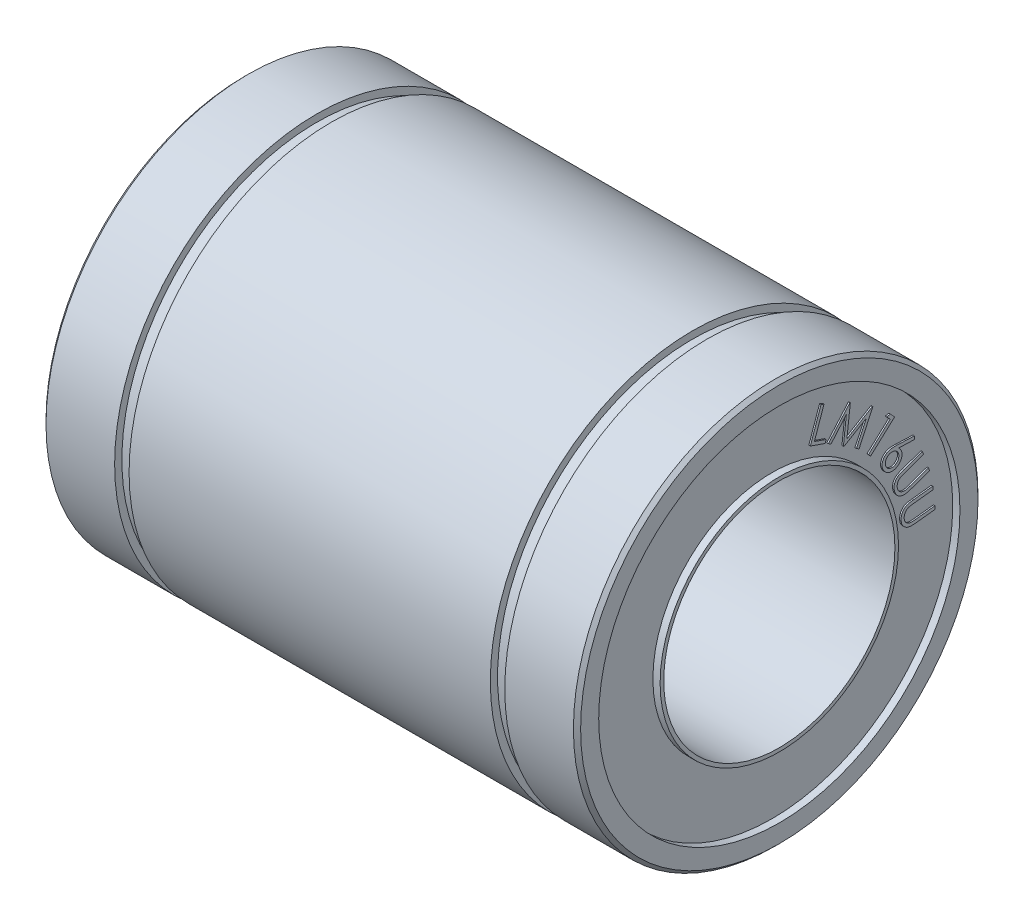
SolidWorks part; units mm, degrees
material "AISI 304"
ref_plane "Front Plane" through (0, 0, 0) normal (0, 0, 1) x (1, 0, 0)
ref_plane "Top Plane" through (0, 0, 0) normal (0, 1, 0) x (1, 0, 0)
ref_plane "Right Plane" through (0, 0, 0) normal (1, 0, 0) x (0, 0, -1)
sketch "Sketch1" plane through (0, 0, 0) normal (1, 0, 0) x (0, 0, -1)
  circle A0 centre (0, 0) radius 14
  dimension "D1" = 28
extrude "Boss-Extrude1" add sketch "Sketch1" along normal blind 37
sketch "Sketch2" plane through (37, 0, 0) normal (1, 0, 0) x (0, 0, -1)
  circle A0 centre (0, 0) radius 8
  dimension "D1" = 16
extrude "Cut-Extrude1" cut sketch "Sketch2" against normal blind 37
sketch "Sketch3" plane through (37, 0, 0) normal (1, 0, 0) x (0, 0, -1)
  circle A0 centre (0, 0) radius 12.5
  circle A1 centre (0, 0) radius 8.25
  dimension "D1" = 16.5
  dimension "D2" = 25
extrude "Cut-Extrude2" cut sketch "Sketch3" against normal blind 0.5
extrude "Cut-Extrude3" cut sketch "Sketch3<2>" against normal blind 0.5 from offset 36.5 offset against normal yes
sketch "Sketch3<2>" plane through (37, 0, 0) normal (1, 0, 0) x (0, 0, -1) same geometry as "Sketch3"
sketch "Sketch4" plane through (0, 0, 0) normal (0, 1, 0) x (1, 0, 0)
  line L0 (31, 13.5) -> (31, 14)
  line L1 (37, 14) -> (0, 14) construction
  line L2 (32, 14) -> (32, 13.5)
  line L3 (32, 13.5) -> (31, 13.5)
  line L4 (37, 14) -> (0, 14) construction
  line L5 (32, 14) -> (31, 14)
  line L6 (37, 0) -> (0, 0) construction
  line L7 (5, 13.5) -> (6, 13.5)
  line L8 (5, 14) -> (5, 13.5)
  line L9 (6, 13.5) -> (6, 14)
  line L10 (6, 14) -> (5, 14)
  dimension "D1" = 0.5
  dimension "D2" = 1
  dimension "D3" = 25
  dimension "D4" = 13.5
  dimension "D5" = 5
  dimension "D6" = 1
revolve "Cut-Revolve1" cut sketch "Sketch4" angle 360 about axis through (37, 0, 0) along (-1, 0, 0)
chamfer "Chamfer1" distance 0.25 angle 45 2 edges at (0, 0, -14) (37, 0, -14)
sketch "Sketch5" plane through (36.5, 0, 0) normal (1, 0, 0) x (0, 0, -1)
  circle A0 centre (0, 0) radius 9 construction
  text T0 "LM16UU" font "Century Gothic" height 2.25
  dimension "D1" = 18
extrude "Boss-Extrude2" add sketch "Sketch5" along normal blind 0.1
sketch "Sketch6" plane through (0.5, 0, 0) normal (-1, 0, 0) x (0, 0, 1)
  circle A0 centre (0, 0) radius 9 construction
  text T0 "LM16UU" font "Century Gothic" height 2.25
  dimension "D1" = 18
extrude "Boss-Extrude3" add sketch "Sketch6" along normal blind 0.1
